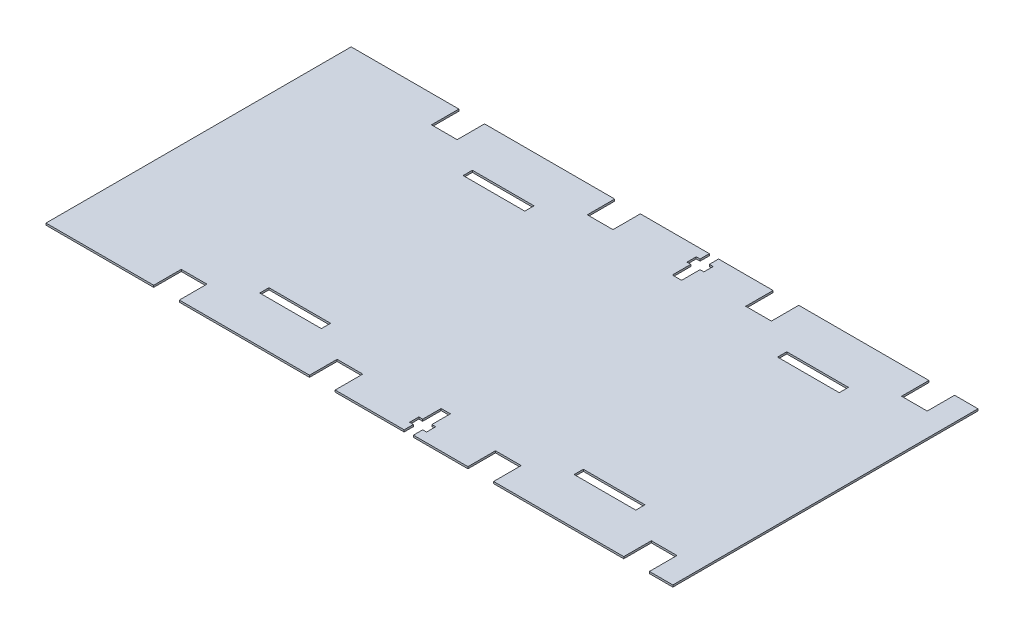
SolidWorks part; units mm, degrees
ref_plane "Front Plane" through (0, 0, 0) normal (0, 0, 1) x (1, 0, 0)
ref_plane "Top Plane" through (0, 0, 0) normal (0, 1, 0) x (1, 0, 0)
ref_plane "Right Plane" through (0, 0, 0) normal (1, 0, 0) x (0, 0, -1)
sketch "Sketch2" plane through (0, 0, 0) normal (0, 1, 0) x (1, 0, 0)
  line L0 (455.3827, -196.3256) -> (455.3827, -239.5823)
  line L1 (415.0808, -196.3256) -> (455.3827, -196.3256)
  line L2 (415.0808, -239.5823) -> (415.0808, -196.3256)
  line L3 (210.7031, -239.5823) -> (415.0808, -239.5823)
  line L4 (210.7031, -196.3256) -> (210.7031, -239.5823)
  line L5 (170.3995, -196.3256) -> (210.7031, -196.3256)
  line L6 (170.3995, -239.5823) -> (170.3995, -196.3256)
  line L7 (84.7783, -239.5823) -> (170.3995, -239.5823)
  line L8 (84.7783, -225.0622) -> (84.7783, -239.5823)
  line L9 (90.8278, -225.0622) -> (84.7783, -225.0622)
  line L10 (90.8278, -210.5422) -> (90.8278, -225.0622)
  line L11 (84.7783, -210.5422) -> (90.8278, -210.5422)
  line L12 (84.7783, -181.5021) -> (84.7783, -210.5422)
  line L13 (70.2566, -181.5021) -> (84.7783, -181.5021)
  line L14 (70.2566, -210.5422) -> (70.2566, -181.5021)
  line L15 (64.2055, -210.5422) -> (70.2566, -210.5422)
  line L16 (64.2055, -225.0622) -> (64.2055, -210.5422)
  line L17 (70.2566, -225.0622) -> (64.2055, -225.0622)
  line L18 (70.2566, -239.5823) -> (70.2566, -225.0622)
  line L19 (-38.04, -239.5823) -> (70.2566, -239.5823)
  line L20 (-38.04, -196.3256) -> (-38.04, -239.5823)
  line L21 (-78.342, -196.3256) -> (-38.04, -196.3256)
  line L22 (-78.342, -239.5823) -> (-78.342, -196.3256)
  line L23 (-282.7213, -239.5823) -> (-78.342, -239.5823)
  line L24 (-282.7213, -196.3256) -> (-282.7213, -239.5823)
  line L25 (-323.0233, -196.3256) -> (-282.7213, -196.3256)
  line L26 (-323.0233, -239.5823) -> (-323.0233, -196.3256)
  line L27 (-492.153, -239.5823) -> (-323.0233, -239.5823)
  line L28 (-492.153, 239.5823) -> (-492.153, -239.5823)
  line L29 (-323.0233, 239.5823) -> (-492.153, 239.5823)
  line L30 (-323.0233, 196.6024) -> (-323.0233, 239.5823)
  line L31 (-282.7213, 196.6024) -> (-323.0233, 196.6024)
  line L32 (-282.7213, 239.5823) -> (-282.7213, 196.6024)
  line L33 (-78.342, 239.5823) -> (-282.7213, 239.5823)
  line L34 (-78.342, 196.6024) -> (-78.342, 239.5823)
  line L35 (-38.04, 196.6024) -> (-78.342, 196.6024)
  line L36 (-38.04, 239.5823) -> (-38.04, 196.6024)
  line L37 (70.2566, 239.5823) -> (-38.04, 239.5823)
  line L38 (70.2566, 225.0622) -> (70.2566, 239.5823)
  line L39 (64.2055, 225.0622) -> (70.2566, 225.0622)
  line L40 (64.2055, 210.5355) -> (64.2055, 225.0622)
  line L41 (70.2566, 210.5355) -> (64.2055, 210.5355)
  line L42 (70.2566, 181.4938) -> (70.2566, 210.5355)
  line L43 (84.7783, 181.4938) -> (70.2566, 181.4938)
  line L44 (84.7783, 210.5355) -> (84.7783, 181.4938)
  line L45 (90.8278, 210.5355) -> (84.7783, 210.5355)
  line L46 (90.8278, 225.0622) -> (90.8278, 210.5355)
  line L47 (84.7783, 225.0622) -> (90.8278, 225.0622)
  line L48 (84.7783, 239.5823) -> (84.7783, 225.0622)
  line L49 (170.3995, 239.5823) -> (84.7783, 239.5823)
  line L50 (170.3995, 196.6024) -> (170.3995, 239.5823)
  line L51 (210.7031, 196.6024) -> (170.3995, 196.6024)
  line L52 (210.7031, 239.5823) -> (210.7031, 196.6024)
  line L53 (415.0808, 239.5823) -> (210.7031, 239.5823)
  line L54 (415.0808, 196.6024) -> (415.0808, 239.5823)
  line L55 (455.3827, 196.6024) -> (415.0808, 196.6024)
  line L56 (455.3827, 239.5823) -> (455.3827, 196.6024)
  line L57 (492.153, 239.5823) -> (455.3827, 239.5823)
  line L58 (492.153, -239.5823) -> (492.153, 239.5823)
  line L59 (455.3827, -239.5823) -> (492.153, -239.5823)
  line L60 (-229.1949, -152.4721) -> (-229.1949, -166.9521)
  line L61 (-229.1949, -166.9521) -> (-132.3936, -166.9521)
  line L62 (-132.3936, -166.9521) -> (-132.3953, -152.4721)
  line L63 (-132.3953, -152.4721) -> (-229.1949, -152.4721)
  line L64 (-229.1949, 166.9754) -> (-229.1949, 152.4987)
  line L65 (-229.1949, 152.4987) -> (-132.3936, 152.4987)
  line L66 (-132.3936, 152.4987) -> (-132.3953, 166.9754)
  line L67 (-132.3953, 166.9754) -> (-229.1949, 166.9754)
  line L68 (264.4913, -152.4721) -> (264.4913, -166.9521)
  line L69 (264.4913, -166.9521) -> (361.2926, -166.9521)
  line L70 (361.2926, -166.9521) -> (361.2926, -152.4721)
  line L71 (361.2926, -152.4721) -> (264.4913, -152.4721)
  line L72 (264.4913, 166.9754) -> (264.4913, 152.4987)
  line L73 (264.4913, 152.4987) -> (361.2926, 152.4987)
  line L74 (361.2926, 152.4987) -> (361.2926, 166.9754)
  line L75 (361.2926, 166.9754) -> (264.4913, 166.9754)
extrude "Boss-Extrude1" add sketch "Sketch2" along normal blind 3
